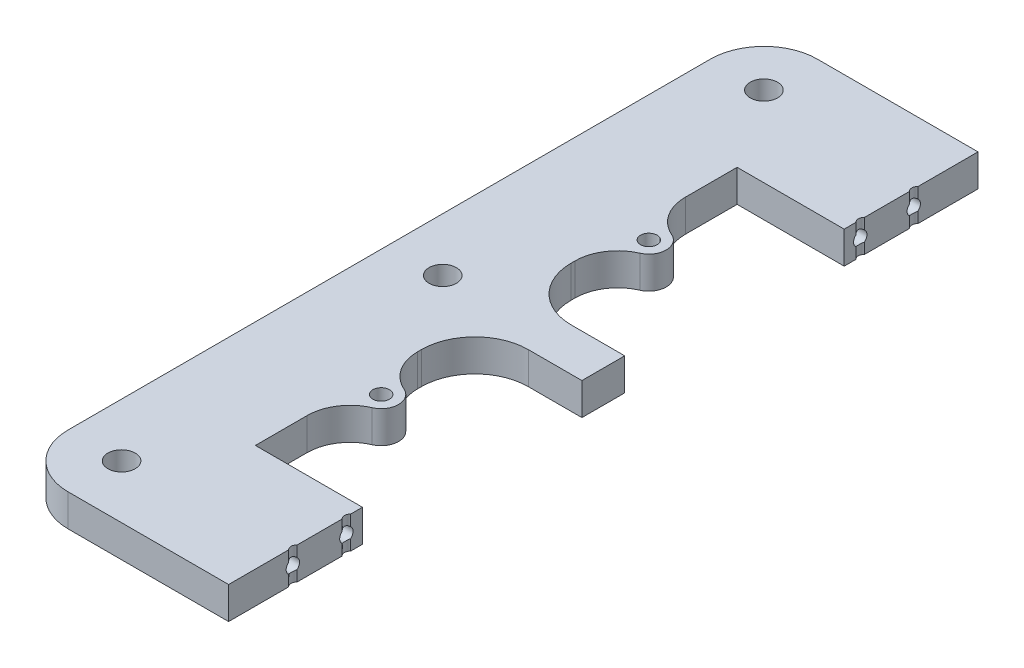
SolidWorks part; units mm, degrees
ref_plane "正面" through (0, 0, 0) normal (0, 0, 1) x (1, 0, 0)
ref_plane "平面" through (0, 0, 0) normal (0, 1, 0) x (1, 0, 0)
ref_plane "右側面" through (0, 0, 0) normal (1, 0, 0) x (0, 0, -1)
sketch "ｽｹｯﾁ1" plane through (0, 0, 0) normal (0, 1, 0) x (1, 0, 0)
  line L0 (0, -70) -> (0, 70)
  line L1 (0, 70) -> (36.5, 70)
  line L2 (36.5, 70) -> (36.5, 61)
  line L3 (36.5, 61) -> (40, 61)
  line L4 (40, 61) -> (40, 45)
  line L5 (40, 45) -> (20, 45)
  line L6 (20, 45) -> (20, -45)
  line L7 (20, 0) -> (0, 0) construction
  line L8 (40, -45) -> (20, -45)
  line L9 (40, -61) -> (40, -45)
  line L10 (36.5, -61) -> (40, -61)
  line L11 (36.5, -70) -> (36.5, -61)
  line L12 (0, -70) -> (36.5, -70)
  dimension "D1" = 140
  dimension "D2" = 9
  dimension "D3" = 3.5
  dimension "D4" = 25
  dimension "D5" = 40
  dimension "D6" = 20
extrude "ﾎﾞｽ - 押し出し1" add sketch "ｽｹｯﾁ1" along normal blind 6
sketch "ｽｹｯﾁ2" plane through (40, 0, 0) normal (1, 0, 0) x (0, 0, -1)
  line L0 (65, 6) -> (65, 0) construction
  line L1 (61, 6) -> (70, 6) construction
  line L2 (61, 0) -> (70, 0) construction
  line L3 (48, 6) -> (48, 0) construction
  line L4 (45, 6) -> (61, 6) construction
  line L5 (45, 0) -> (61, 0) construction
  line L6 (70, 6) -> (70, 0) construction
  line L7 (0, 0) -> (0, 6) construction
  line L8 (-45, 6) -> (45, 6) construction
  line L9 (58, 6) -> (58, 0) construction
  line L10 (53, 6) -> (53, 0) construction
  line L11 (48, 3) -> (53, 3) construction
  line L12 (53, 3) -> (58, 3) construction
  circle A0 centre (65, 3) radius 1.25 construction
  circle A1 centre (48, 3) radius 1.25
  circle A2 centre (58, 3) radius 1.25
  circle A3 centre (-48, 3) radius 1.25
  circle A4 centre (-58, 3) radius 1.25
  circle A5 centre (-65, 3) radius 1.25 construction
  dimension "D1" = 2.5
  dimension "D2" = 2.5
  dimension "D5" = 2.5
  dimension "D3" = 22
  dimension "D4" = 5
extrude "ｶｯﾄ - 押し出し1" cut sketch "ｽｹｯﾁ2" against normal blind 10
sketch "ｽｹｯﾁ3" plane through (0, 6, 0) normal (0, 1, 0) x (1, 0, 0)
  line L0 (36.5, 65) -> (37.2, 65) construction
  line L1 (36.5, 61) -> (36.5, 70) construction
  line L2 (40, 48) -> (40.7, 48) construction
  line L3 (40.7, 58) -> (40, 58) construction
  line L4 (40, 45) -> (40, 61) construction
  line L5 (36.5, 70) -> (0, 70) construction
  line L6 (40, 53) -> (40.7, 53) construction
  line L7 (40, 58) -> (40, 53) construction
  line L8 (40, 53) -> (40, 48) construction
  line L9 (0, 0) -> (20, 0) construction
  line L10 (20, -45) -> (20, 45) construction
  circle A0 centre (37.2, 65) radius 1.05 construction
  circle A1 centre (40.7, 58) radius 1.05
  circle A2 centre (40.7, 48) radius 1.05
  circle A3 centre (40.7, -48) radius 1.05
  circle A4 centre (40.7, -58) radius 1.05
  circle A5 centre (37.2, -65) radius 1.05 construction
  dimension "D3" = 2.1
  dimension "D1" = 5
  dimension "D2" = 22
  dimension "D4" = 0.7
extrude "ｶｯﾄ - 押し出し2" cut sketch "ｽｹｯﾁ3" against normal through all
sketch "ｽｹｯﾁ4" plane through (0, 6, 0) normal (0, 1, 0) x (1, 0, 0)
  line L0 (10, 70) -> (10, -70) construction
  line L1 (36.5, 70) -> (0, 70) construction
  line L2 (0, -70) -> (36.5, -70) construction
  line L3 (0, 0) -> (10, 0) construction
  line L4 (10, 0) -> (20, 0) construction
  line L5 (20, -45) -> (20, 45) construction
  circle A0 centre (10, 0) radius 2.55
  circle A1 centre (10, 60) radius 2.55
  circle A2 centre (10, -60) radius 2.55
  dimension "D1" = 5.1
  dimension "D2" = 10
  dimension "D3" = 10
extrude "ｶｯﾄ - 押し出し3" cut sketch "ｽｹｯﾁ4" against normal through all
fillet "ﾌｨﾚｯﾄ1" [suppressed] radius 2.1
sketch "ｽｹｯﾁ5" plane through (20, 0, 0) normal (1, 0, 0) x (0, 0, -1)
  line L0 (-45, 0) -> (45, 0) construction
  line L1 (-4, 6) -> (4, 6)
  line L2 (-4, 6) -> (-4, 0)
  line L3 (-4, 0) -> (4, 0)
  line L4 (4, 6) -> (4, 0)
  line L5 (-4, 6) -> (4, 0) construction
  line L6 (-4, 0) -> (4, 6) construction
  line L7 (-45, 6) -> (45, 6) construction
  point P0 (0, 3)
  dimension "D1" = 8
extrude "ﾎﾞｽ - 押し出し2" add sketch "ｽｹｯﾁ5" along normal up to surface (20 mm away) up to face at (40, 3, -53)
fillet "ﾌｨﾚｯﾄ2" radius 10 2 edges at (20, 3, 4) (20, 3, -4)
fillet "ﾌｨﾚｯﾄ3" radius 10 2 edges at (0, 3, 70) (0, 3, -70)
sketch "ｽｹｯﾁ7" plane through (0, 6, 0) normal (0, 1, 0) x (1, 0, 0)
  line L0 (0, 0) -> (40, 0) construction
  line L1 (0, 60) -> (0, -60) construction
  line L2 (40, -4) -> (40, 4) construction
  line L3 (0, 25) -> (40.5945, 25) construction
  line L4 (23.5, 28.25) -> (20, 28.25)
  line L5 (20, 14) -> (20, 45) construction
  line L6 (20, 28.25) -> (20, 21.75)
  line L7 (20, 21.75) -> (23.5, 21.75)
  line L8 (0, -25) -> (40.5945, -25) construction
  line L9 (20, -21.75) -> (23.5, -21.75)
  line L10 (20, -28.25) -> (20, -21.75)
  line L11 (23.5, -28.25) -> (20, -28.25)
  circle A0 centre (23.5, 25) radius 1.55
  arc A1 (23.5, 28.25) -> (23.5, 21.75) centre (23.5, 25) cw
  arc A2 (23.5, -28.25) -> (23.5, -21.75) centre (23.5, -25) ccw
  circle A3 centre (23.5, -25) radius 1.55
  dimension "D1" = 3.1
  dimension "D2" = 6.5
  dimension "D3" = 3.5
  dimension "D4" = 25
extrude "ﾎﾞｽ - 押し出し3" add sketch "ｽｹｯﾁ7" against normal through all
fillet "ﾌｨﾚｯﾄ4" radius 8 4 edges at (20, 3, 28.25) (20, 3, 21.75) (20, 3, -28.25) (20, 3, -21.75)
sketch "ｽｹｯﾁ8" plane through (0, 0, 0) normal (0, 1, 0) x (1, 0, 0)
  circle A0 centre (23.5, 25) radius 3.25
  circle A1 centre (23.5, -25) radius 3.25
  arc A2 (24.8, 22.0213) -> (24.8, 27.9787) centre (23.5, 25) ccw construction
  arc A3 (24.8, -27.9787) -> (24.8, -22.0213) centre (23.5, -25) ccw construction
extrude "ｶｯﾄ - 押し出し4" [suppressed] cut sketch "ｽｹｯﾁ8" along normal blind 3
fillet "ﾌｨﾚｯﾄ5" [suppressed] radius 1
sketch "ｽｹｯﾁ9" plane through (36.5, 0, 0) normal (1, 0, 0) x (0, 0, -1)
  line L0 (-70, 0) -> (-61, 0) construction
  line L1 (-61, 0) -> (-61, 6) construction
  line L2 (-61, 6) -> (-70, 6) construction
  line L3 (-70, 6) -> (-70, 0) construction
  line L4 (61, 0) -> (70, 0) construction
  line L5 (70, 0) -> (70, 6) construction
  line L6 (70, 6) -> (61, 6) construction
  line L7 (61, 6) -> (61, 0) construction
  line L8 (-70, 0) -> (-61, 0)
  line L9 (-61, 0) -> (-61, 6)
  line L10 (-61, 6) -> (-70, 6)
  line L11 (-70, 6) -> (-70, 0)
  line L12 (61, 0) -> (70, 0)
  line L13 (70, 0) -> (70, 6)
  line L14 (70, 6) -> (61, 6)
  line L15 (61, 6) -> (61, 0)
extrude "ﾎﾞｽ - 押し出し4" add sketch "ｽｹｯﾁ9" along normal up to surface (3.5 mm away) up to face at (40, 3, -53)
